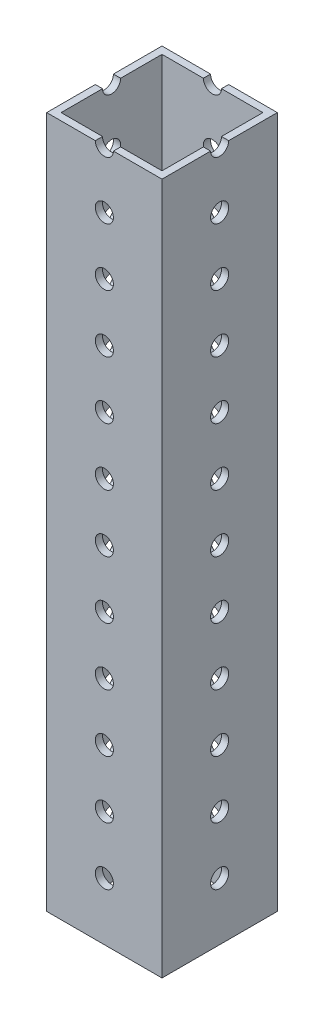
SolidWorks part; units mm, degrees
material "6061-T6 (SS)"
ref_plane "Front Plane" through (0, 0, 0) normal (0, 0, 1) x (1, 0, 0)
ref_plane "Top Plane" through (0, 0, 0) normal (0, 1, 0) x (1, 0, 0)
ref_plane "Right Plane" through (0, 0, 0) normal (1, 0, 0) x (0, 0, -1)
sketch "Sketch1" plane through (0, 0, 0) normal (0, 1, 0) x (1, 0, 0)
  line L0 (-11.1125, -11.1125) -> (-11.1125, 11.1125)
  line L1 (-12.7, -12.7) -> (12.7, -12.7)
  line L2 (-12.7, -12.7) -> (-12.7, 12.7)
  line L3 (-12.7, 12.7) -> (12.7, 12.7)
  line L4 (12.7, -12.7) -> (12.7, 12.7)
  line L5 (-12.7, -12.7) -> (12.7, 12.7) construction
  line L6 (-12.7, 12.7) -> (12.7, -12.7) construction
  line L7 (-11.1125, 11.1125) -> (11.1125, 11.1125)
  line L8 (11.1125, -11.1125) -> (11.1125, 11.1125)
  line L9 (-11.1125, -11.1125) -> (11.1125, -11.1125)
  point P0 (0, 0)
  dimension "D1" = 25.4
  dimension "D2" = 25.4
  dimension "D3" = 1.5875
extrude "Boss-Extrude1" add sketch "Sketch1" along normal blind 152.4
hole_wizard "#22 (0.157) Diameter Hole1" positions "Sketch2" profile "Sketch3" hole size "#22" standard "ANSI Inch" end condition through all
sketch "Sketch2" plane through (0, 0, 12.7) normal (0, 0, 1) x (1, 0, 0)
  line L0 (12.7, 152.4) -> (12.7, 0) construction
  line L1 (-12.7, 0) -> (12.7, 0) construction
  point P0 (0, 12.7)
  dimension "D1" = 12.7
  dimension "D2" = 12.7
sketch "Sketch3" plane through (0, 12.7, 12.7) normal (1, 0, 0) x (0, -1, 0)
  line L0 (0, 0) -> (0, 25.4)
  line L1 (0, 25.4) -> (1.9939, 25.4)
  line L2 (1.9939, 25.4) -> (1.9939, 0)
  line L5 (1.9939, 0) -> (0, 0)
  line L11 (0, -6.35) -> (0, 107.95) construction
  dimension "Thru Hole Dia." = 3.9878
  dimension "Thru Hole Depth" = 25.4
pattern_linear "LPattern1" count 12 spacing 12.7 along (0, 1, 0) of "#22 (0.157) Diameter Hole1"
hole_wizard "#22 (0.157) Diameter Hole2" positions "Sketch4" profile "Sketch5" hole size "#22" standard "ANSI Inch" end condition through all
sketch "Sketch4" plane through (12.7, 0, 0) normal (1, 0, 0) x (0, 0, -1)
  line L2 (-12.7, 152.4) -> (-12.7, 0) construction
  line L3 (-12.7, 0) -> (12.7, 0) construction
  point P0 (0, 12.7)
  dimension "D1" = 12.7
  dimension "D2" = 12.7
sketch "Sketch5" plane through (12.7, 12.7, 0) normal (0, 1, 0) x (0, 0, -1)
  line L0 (0, 0) -> (0, 25.4)
  line L1 (0, 25.4) -> (1.9939, 25.4)
  line L2 (1.9939, 25.4) -> (1.9939, 0)
  line L5 (1.9939, 0) -> (0, 0)
  line L11 (0, -6.35) -> (0, 107.95) construction
  dimension "Thru Hole Dia." = 3.9878
  dimension "Thru Hole Depth" = 25.4
pattern_linear "LPattern2" count 12 spacing 12.7 along (0, 1, 0) of "#22 (0.157) Diameter Hole2"
